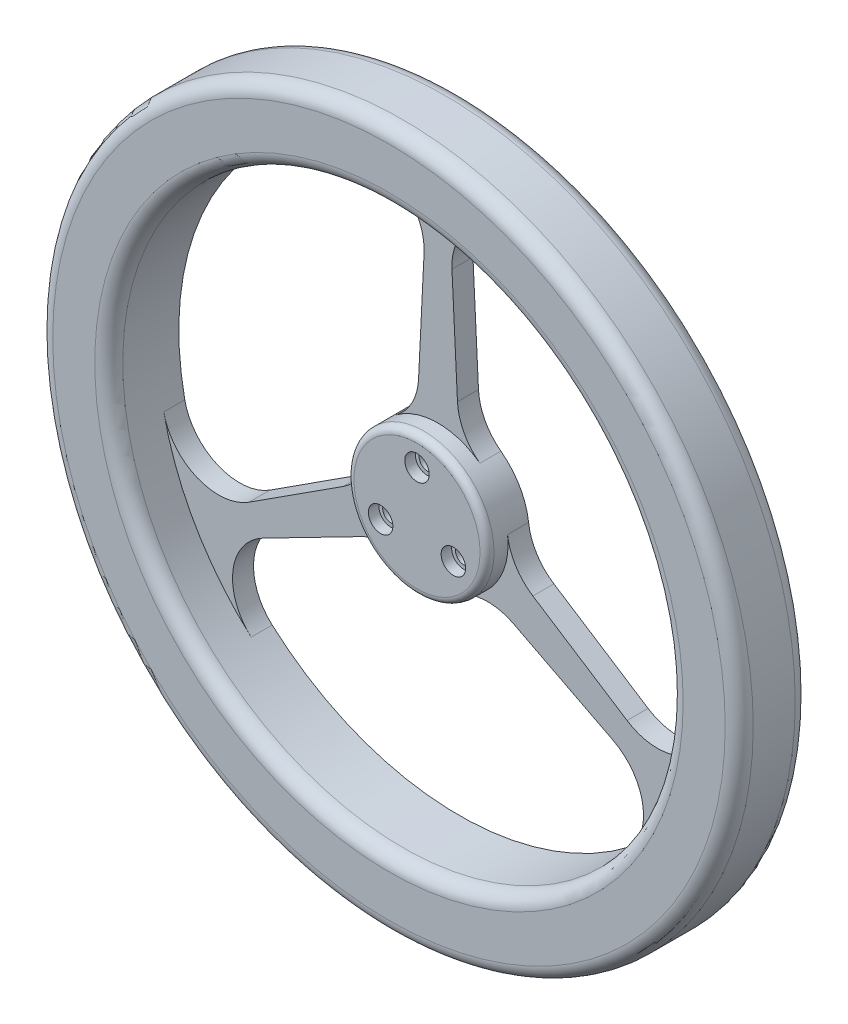
SolidWorks part; units mm, degrees
ref_plane "Front Plane" through (0, 0, 0) normal (0, 0, 1) x (1, 0, 0)
ref_plane "Top Plane" through (0, 0, 0) normal (0, 1, 0) x (1, 0, 0)
ref_plane "Right Plane" through (0, 0, 0) normal (1, 0, 0) x (0, 0, -1)
sketch "Sketch1" plane through (0, 0, 0) normal (0, 0, 1) x (1, 0, 0)
  circle A0 centre (0, 0) radius 50
  dimension "D1" = 100
extrude "Extrude-Thin1" add sketch "Sketch1" along normal blind 10 thin thin type one direction reverse wall 10
sketch "Sketch2" plane through (0, 0, 0) normal (0, 0, 1) x (1, 0, 0)
  circle A0 centre (0, 0) radius 10
  dimension "D2" = 20
extrude "Boss-Extrude1" add sketch "Sketch2" along normal blind 6 separate body contours A0 region at (0, 0, 0)
sketch "Sketch3" plane through (0, 0, 0) normal (0, 0, 1) x (1, 0, 0)
  line L0 (0, -40) -> (0, 40) construction
  line L1 (-1.4997, 39.9719) -> (-3, 9.5394)
  line L2 (1.4997, 39.9719) -> (3, 9.5394)
  line L3 (35.3665, -18.6871) -> (9.7614, -2.1716)
  line L4 (33.8668, -21.2847) -> (6.7614, -7.3678)
  line L5 (-33.8668, -21.2847) -> (-6.7614, -7.3678)
  line L6 (-35.3665, -18.6871) -> (-9.7614, -2.1716)
  circle A0 centre (0, 0) radius 40
  circle A1 centre (0, 0) radius 40 construction
  circle A2 centre (0, 0) radius 10
  circle A4 centre (0, 0) radius 10 construction
  point P8 (0, 0)
  point P9 (0, 0)
  point P10 (0, 0)
  point P15 (0, 0)
  point P40 (0, 0)
  dimension "D1" = 1.5
  dimension "D2" = 3
  dimension "D3" = 3
extrude "Boss-Extrude4" add sketch "Sketch3" along normal blind 3 contours A2 L0 A0 L1 | L0 A2 L2 A0 | A2 L4 A0 L3 | A2 L6 A0 L5 region at (-20.1388, -11.6272, 0) region at (20.1388, -11.6272, 0) region at (-1.1669, 23.2543, 0) region at (1.1669, 23.2543, 0)
sketch "Sketch4" plane through (0, 0, 6) normal (0, 0, 1) x (1, 0, 0)
  line L0 (0, 0) -> (0, 6) construction
  line L1 (0, 0) -> (-5.1962, -3) construction
  line L2 (0, 0) -> (5.1962, -3) construction
  circle A0 centre (0, 0) radius 6
  dimension "D1" = 12
  dimension "D2" = 120
  dimension "D3" = 120
hole_wizard "M2 Clearance Hole1" positions "Sketch5" profile "Sketch6" hole size "M2" standard "ANSI Metric"
sketch "Sketch5" plane through (0, 0, 6) normal (0, 0, 1) x (1, 0, 0)
  point P0 (0, 6)
  point P3 (-5.1962, -3)
  point P6 (5.1962, -3)
sketch "Sketch6" plane through (0, 6, 6) normal (1, 0, 0) x (0, -1, 0)
  line L0 (0, 0) -> (0, 10.721)
  line L1 (0, 10.721) -> (1.2, 10)
  line L2 (1.2, 10) -> (1.2, 0)
  line L5 (1.2, 0) -> (0, 0)
  line L10 (0, 10.721) -> (-1.2, 10) construction
  line L11 (0, -6.35) -> (0, 107.95) construction
  dimension "Hole Dia." = 2.4
  dimension "Hole Depth" = 10
  dimension "Drill Angle" = 118
fillet "Fillet4" radius 8 12 edges at (35.3665, -18.6871, 1.5) (33.8668, -21.2847, 1.5) (-33.8668, -21.2847, 1.5) (-35.3665, -18.6871, 1.5) (6.7614, -7.3678, 1.5) (-6.7614, -7.3678, 1.5) (-9.7614, -2.1716, 1.5) (-3, 9.5394, 1.5) (9.7614, -2.1716, 1.5) (3, 9.5394, 1.5) (1.4997, 39.9719, 1.5) (-1.4997, 39.9719, 1.5)
fillet "Fillet2" radius 1 1 edges at (10, 0, 6)
fillet "Fillet3" radius 2 3 edges at (50, 0, 0) (50, 0, 10) (40, 0, 10)
sketch "Sketch7" plane through (0, 0, 0) normal (0, 0, -1) x (-1, 0, 0)
  circle A0 centre (0, 0) radius 4.6
  dimension "D1" = 9.2
extrude "Cut-Extrude1" cut sketch "Sketch7" against normal blind 4
sketch "Sketch8" plane through (0, 0, 6) normal (0, 0, 1) x (1, 0, 0)
  circle A0 centre (0, 6) radius 1.75
  dimension "D1" = 3.5
extrude "Cut-Extrude2" cut sketch "Sketch8" against normal blind 1.5
pattern_circular "CirPattern1" count 3 over 360 about axis through (0, 0, 6) along (0, 0, 1) of "Cut-Extrude2"
